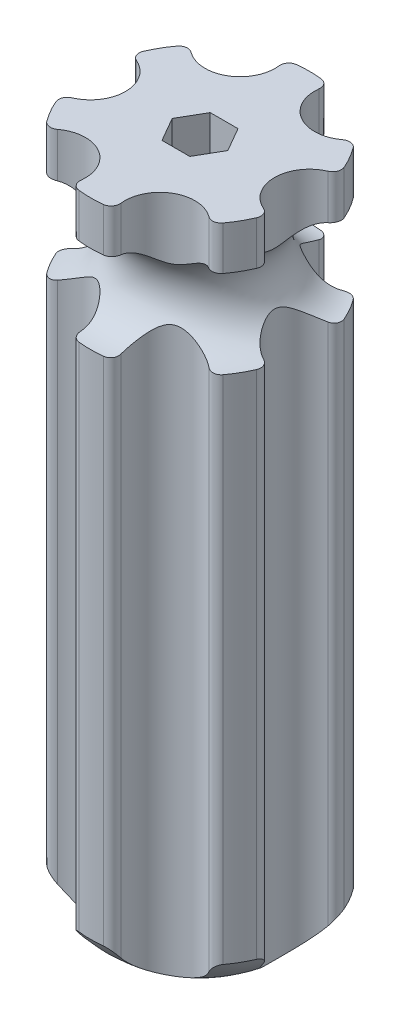
SolidWorks part; units mm, degrees
ref_plane "Front Plane" through (0, 0, 0) normal (0, 0, 1) x (1, 0, 0)
ref_plane "Top Plane" through (0, 0, 0) normal (0, 1, 0) x (1, 0, 0)
ref_plane "Right Plane" through (0, 0, 0) normal (1, 0, 0) x (0, 0, -1)
sketch "Sketch1" plane through (0, 0, 0) normal (0, 0, 1) x (1, 0, 0)
  line L0 (-6.25, 35) -> (-6.25, 40)
  line L2 (-6.25, -33.2916) -> (-6.25, 25)
  line L3 (-6.25, 40) -> (6.25, 40)
  line L4 (6.25, -40) -> (6.25, 40)
  line L5 (-6.25, -40) -> (6.25, 40) construction
  line L6 (-6.25, 40) -> (6.25, -40) construction
  arc A0 (-6.25, -33.2916) -> (6.25, -40) centre (6.25, -25) ccw
  arc A1 (-6.25, 25) -> (-6.25, 35) centre (-6.25, 30) ccw
  point P0 (0, 0)
  dimension "D1" = 80
  dimension "D2" = 12.5
revolve "Revolve1" add sketch "Sketch1" angle 360 about L4
sketch "Sketch2" plane through (0, 40, 0) normal (0, 1, 0) x (1, 0, 0)
  line L0 (6.25, 0) -> (18.75, 0)
  circle A0 centre (6.25, 0) radius 12.5
  circle A1 centre (18.75, 0) radius 4
  circle A2 centre (12.5, -10.8253) radius 4
  circle A3 centre (0, -10.8253) radius 4
  circle A4 centre (-6.25, 0) radius 4
  circle A5 centre (0, 10.8253) radius 4
  circle A6 centre (12.5, 10.8253) radius 4
  point P17 (6.25, 0)
  dimension "D1" = 8
  dimension "D2" = 6
extrude "Cut-Extrude1" cut sketch "Sketch2" against normal blind 80 contours A5 | A6 | A1 | A2 | A3 | A4
fillet "Fillet1" radius 1 24 edges at (8.7605, 37.5, 12.2453) (15.5995, 37.5, 8.2968) (3.7395, 37.5, 12.2453) (-3.0995, 37.5, 8.2968) (-5.61, 37.5, 3.9485) (-5.61, 37.5, -3.9485) (-3.0995, 37.5, -8.2968) (3.7395, 37.5, -12.2453) (8.7605, 37.5, -12.2453) (18.11, 37.5, 3.9485) (18.11, 37.5, -3.9485) (15.5995, 37.5, -8.2968) (-3.0995, -4.1458, -8.2968) (-5.61, -4.1458, -3.9485) (-5.61, -4.1458, 3.9485) (-3.0995, -4.1458, 8.2968) (3.7395, -4.1458, 12.2453) (8.7605, -4.1458, 12.2453) (15.5995, -4.1458, 8.2968) (18.11, -4.1458, 3.9485) (18.11, -4.1458, -3.9485) (15.5995, -4.1458, -8.2968) (3.7395, -4.1458, -12.2453) (8.7605, -4.1458, -12.2453)
sketch "Sketch3" plane through (0, 0, 0) normal (0, 1, 0) x (1, 0, 0)
  line L1 (9.425, 0) -> (7.8375, 2.7496)
  line L2 (7.8375, 2.7496) -> (4.6625, 2.7496)
  line L3 (4.6625, 2.7496) -> (3.075, 0)
  line L4 (3.075, 0) -> (4.6625, -2.7496)
  line L5 (4.6625, -2.7496) -> (7.8375, -2.7496)
  line L6 (7.8375, -2.7496) -> (9.425, 0)
  circle A1 centre (6.25, 0) radius 2.7496 construction
extrude "Cut-Extrude3" cut sketch "Sketch3" along normal blind 75
